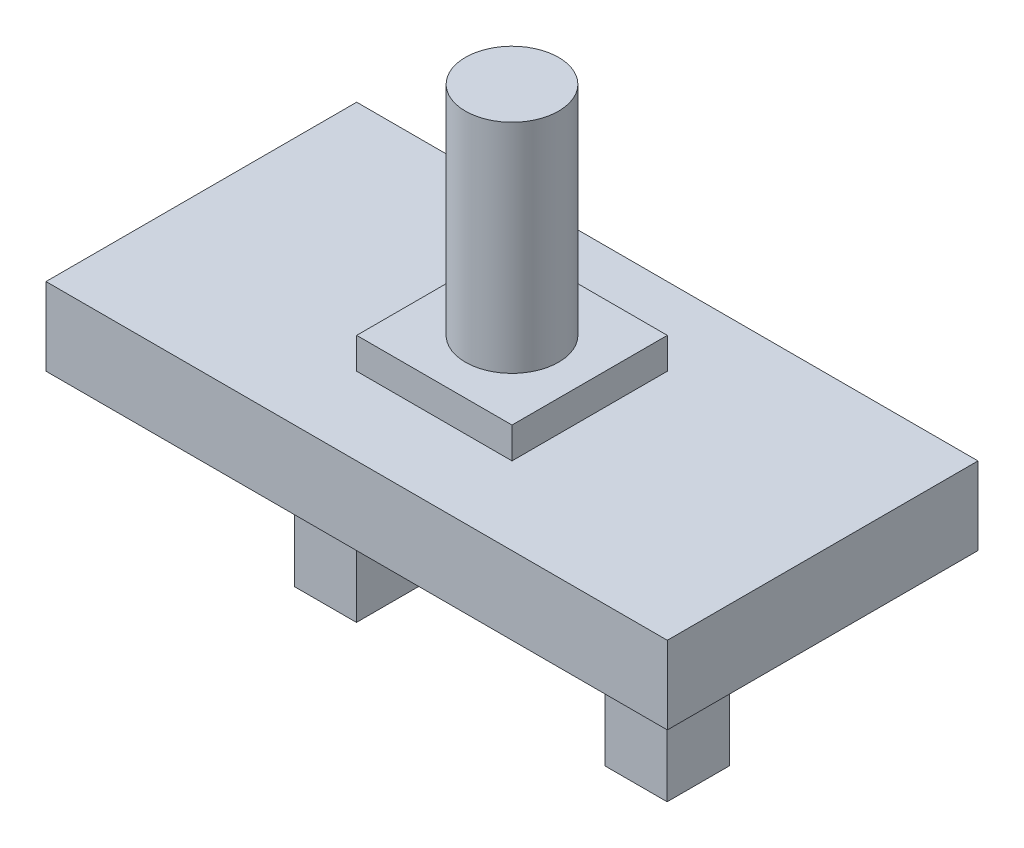
SolidWorks part; units mm, degrees
ref_plane "Front Plane" through (0, 0, 0) normal (0, 0, 1) x (1, 0, 0)
ref_plane "Top Plane" through (0, 0, 0) normal (0, 1, 0) x (1, 0, 0)
ref_plane "Right Plane" through (0, 0, 0) normal (1, 0, 0) x (0, 0, -1)
sketch "Sketch2" plane through (0, 0, 0) normal (0, 1, 0) x (1, 0, 0)
  line L1 (-1000, 500) -> (1000, 500)
  line L2 (-1000, 500) -> (-1000, -500)
  line L3 (-1000, -500) -> (1000, -500)
  line L4 (1000, 500) -> (1000, -500)
  line L5 (-1000, 500) -> (1000, -500) construction
  line L6 (-1000, -500) -> (1000, 500) construction
  point P0 (0, 0)
  dimension "D1" = 2000
  dimension "D2" = 1000
extrude "Boss-Extrude1" add sketch "Sketch2" along normal blind 250
sketch "Sketch3" plane through (0, 0, 0) normal (0, -1, 0) x (1, 0, 0)
  line L4 (-250, -251.5808) -> (-750, -251.5808)
  line L5 (-250, -251.5808) -> (-250, 251.5808)
  line L6 (250, 251.5808) -> (750, 251.5808)
  line L7 (250, 251.5808) -> (250, -251.5808)
  line L8 (250, -251.5808) -> (750, -251.5808)
  line L9 (750, 251.5808) -> (750, -251.5808)
  line L10 (250, 251.5808) -> (750, -251.5808) construction
  line L11 (250, -251.5808) -> (750, 251.5808) construction
  line L12 (-250, 251.5808) -> (-750, 251.5808)
  line L13 (-750, -251.5808) -> (-750, 251.5808)
  line L14 (-250, -251.5808) -> (-750, 251.5808) construction
  line L15 (-250, 251.5808) -> (-750, -251.5808) construction
extrude "Boss-Extrude2" add sketch "Sketch3" along normal blind 100
sketch "Sketch4" plane through (0, -100, 0) normal (0, -1, 0) x (1, 0, 0)
  line L5 (600, -100.6323) -> (400, -100.6323)
  line L6 (600, -100.6323) -> (600, 100.6323)
  line L7 (600, 100.6323) -> (400, 100.6323)
  line L8 (400, -100.6323) -> (400, 100.6323)
  line L9 (600, -100.6323) -> (400, 100.6323) construction
  line L10 (600, 100.6323) -> (400, -100.6323) construction
  point P2 (500, 0)
  dimension "D1" = 200
extrude "Boss-Extrude3" add sketch "Sketch4" along normal blind 500 contours L8 L7 L6 L5
sketch "Sketch5" plane through (0, -100, 0) normal (0, -1, 0) x (1, 0, 0)
  line L3 (-600, 100.6323) -> (-400, 100.6323)
  line L4 (-600, 100.6323) -> (-600, -100.6323)
  line L5 (-600, -100.6323) -> (-400, -100.6323)
  line L6 (-400, 100.6323) -> (-400, -100.6323)
  line L7 (-600, 100.6323) -> (-400, -100.6323) construction
  line L8 (-600, -100.6323) -> (-400, 100.6323) construction
  point P8 (-500, 0)
extrude "Boss-Extrude4" add sketch "Sketch5" along normal blind 500
sketch "Sketch6" plane through (0, 250, 0) normal (0, 1, 0) x (1, 0, 0)
  line L3 (250, -250) -> (-250, -250)
  line L4 (250, -250) -> (250, 250)
  line L5 (250, 250) -> (-250, 250)
  line L6 (-250, -250) -> (-250, 250)
  line L7 (250, -250) -> (-250, 250) construction
  line L8 (250, 250) -> (-250, -250) construction
  point P8 (0, 0)
extrude "Boss-Extrude5" add sketch "Sketch6" along normal blind 100
sketch "Sketch7" plane through (0, 350, 0) normal (0, 1, 0) x (1, 0, 0)
  circle A0 centre (0, 0) radius 150
extrude "Boss-Extrude6" add sketch "Sketch7" along normal blind 700
